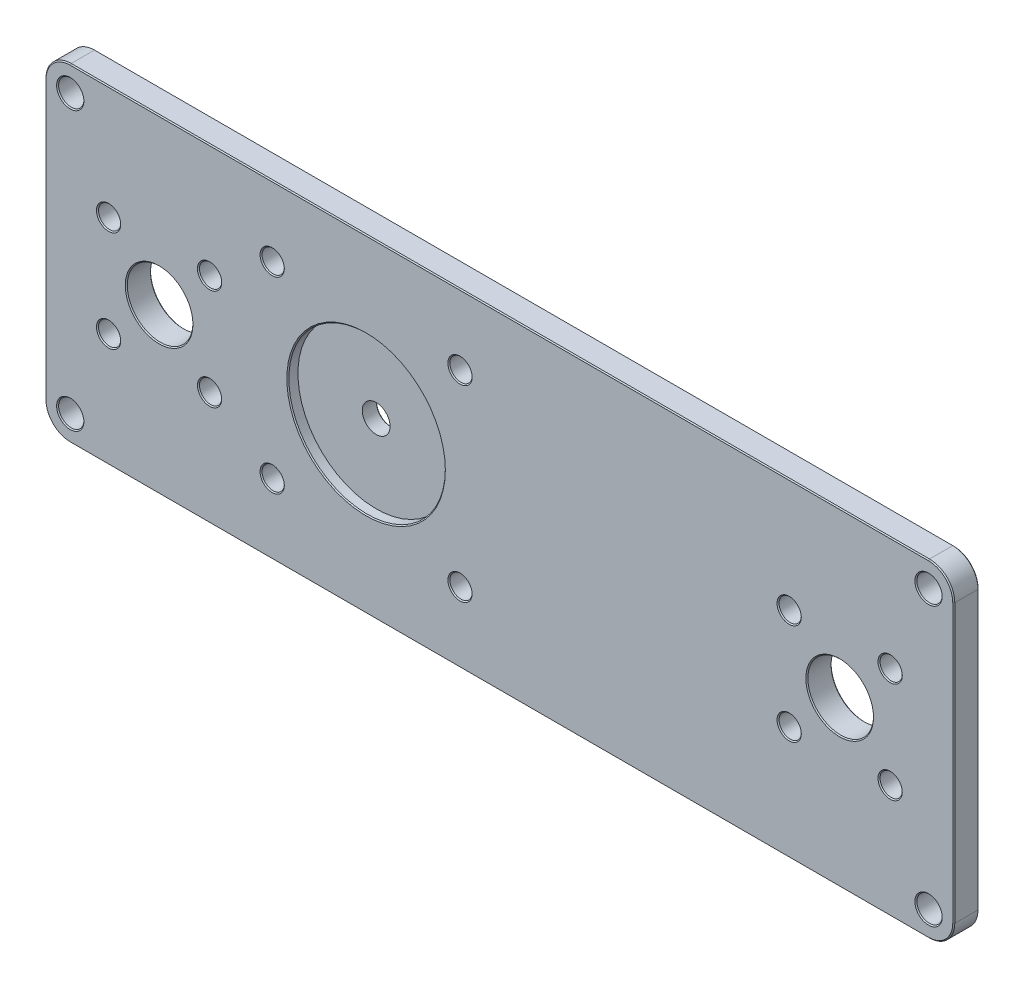
SolidWorks part; units mm, degrees
material "1060 Alloy"
ref_plane "Front Plane" through (0, 0, 0) normal (0, 0, 1) x (1, 0, 0)
ref_plane "Top Plane" through (0, 0, 0) normal (0, 1, 0) x (1, 0, 0)
ref_plane "Right Plane" through (0, 0, 0) normal (1, 0, 0) x (0, 0, -1)
sketch "Sketch3" plane through (0, 0, 0) normal (0, 0, 1) x (1, 0, 0)
  line L0 (-57.15, 23.622) -> (-57.15, -23.622) construction
  line L1 (107.95, -41.275) -> (-107.95, -41.275)
  line L2 (114.3, -34.925) -> (114.3, 34.925)
  line L3 (107.95, 41.275) -> (-107.95, 41.275)
  line L4 (-114.3, -34.925) -> (-114.3, 34.925)
  line L5 (114.3, -41.275) -> (-114.3, 41.275) construction
  line L6 (114.3, 41.275) -> (-114.3, -41.275) construction
  line L7 (-57.15, -23.622) -> (-9.906, -23.622) construction
  line L8 (-9.906, -23.622) -> (-9.906, 23.622) construction
  line L9 (-9.906, 23.622) -> (-57.15, 23.622) construction
  line L10 (-57.15, 23.622) -> (-9.906, -23.622) construction
  line L11 (-9.906, 23.622) -> (-57.15, -23.622) construction
  line L12 (72.898, 12.7) -> (72.898, -12.7) construction
  line L13 (72.898, -12.7) -> (98.298, -12.7) construction
  line L14 (98.298, -12.7) -> (98.298, 12.7) construction
  line L15 (98.298, 12.7) -> (72.898, 12.7) construction
  line L16 (72.898, 12.7) -> (98.298, -12.7) construction
  line L17 (98.298, 12.7) -> (72.898, -12.7) construction
  line L18 (-98.298, 12.7) -> (-72.898, 12.7) construction
  line L19 (-72.898, 12.7) -> (-72.898, -12.7) construction
  line L20 (-72.898, -12.7) -> (-98.298, -12.7) construction
  line L21 (-98.298, -12.7) -> (-98.298, 12.7) construction
  line L22 (-98.298, 12.7) -> (-72.898, -12.7) construction
  line L23 (-72.898, 12.7) -> (-98.298, -12.7) construction
  arc A0 (114.3, 34.925) -> (107.95, 41.275) centre (107.95, 34.925) ccw
  arc A1 (107.95, -41.275) -> (114.3, -34.925) centre (107.95, -34.925) ccw
  arc A2 (-107.95, -41.275) -> (-114.3, -34.925) centre (-107.95, -34.925) cw
  arc A3 (-107.95, 41.275) -> (-114.3, 34.925) centre (-107.95, 34.925) ccw
  circle A4 centre (-57.15, 23.622) radius 2.794
  circle A5 centre (-9.906, 23.622) radius 2.794
  circle A6 centre (-9.906, -23.622) radius 2.794
  circle A7 centre (-57.15, -23.622) radius 2.794
  circle A8 centre (-107.95, 34.925) radius 3.175
  circle A9 centre (-107.95, -34.925) radius 3.175
  circle A10 centre (107.95, -34.925) radius 3.175
  circle A11 centre (107.95, 34.925) radius 3.175
  circle A12 centre (-33.528, 0) radius 3.4925
  circle A13 centre (-33.528, 0) radius 19.685
  circle A14 centre (85.598, 0) radius 8.255
  circle A15 centre (72.898, 12.7) radius 2.794
  circle A16 centre (98.298, 12.7) radius 2.794
  circle A17 centre (98.298, -12.7) radius 2.794
  circle A18 centre (72.898, -12.7) radius 2.794
  circle A19 centre (-85.598, 0) radius 8.255
  circle A20 centre (-72.898, -12.7) radius 2.794
  circle A21 centre (-72.898, 12.7) radius 2.794
  circle A22 centre (-98.298, 12.7) radius 2.794
  circle A23 centre (-98.298, -12.7) radius 2.794
  point P0 (0, 0)
  point P22 (-114.3, 0)
  point P23 (-57.15, 0)
  point P38 (114.3, 0)
  point P43 (85.598, 0)
  point P57 (-98.298, 0)
  dimension "D3" = 6.35
  dimension "D6" = 5.588
  dimension "D7" = 6.35
  dimension "D8" = 39.37
  dimension "D9" = 6.985
  dimension "D10" = 16.51
  dimension "D11" = 28.702
  dimension "D13" = 5.588
  dimension "D14" = 25.4
  dimension "D15" = 5.588
  dimension "D16" = 16.51
  dimension "D1" = 82.55
  dimension "D2" = 228.6
  dimension "D4" = 47.244
  dimension "D5" = 57.15
  dimension "D12" = 25.4
  dimension "D17" = 28.702
extrude "Boss-Extrude1" add sketch "Sketch3" along normal blind 6.35 contours L3 A3 L4 A2 L1 A1 L2 A0 A13 A11 A10 A9 A8 A7 A6 A5 A4 region at (2.63, 0, 0)
extrude "Boss-Extrude2" add sketch "Sketch3<4>" along normal blind 3.81 contours A13 A12 region at (-52.6562, 0, 0)
sketch "Sketch3<4>" plane through (0, 0, 0) normal (0, 0, 1) x (1, 0, 0) same geometry as "Sketch3"
chamfer "Chamfer1" distance 0.254 angle 45 54 edges at (-30.0355, 0, 0) (-112.4401, 39.4151, 0) (-114.3, 0, 0) (-112.4401, -39.4151, 0) (0, -41.275, 0) (112.4401, -39.4151, 0) (114.3, 0, 0) (112.4401, 39.4151, 0) (0, 41.275, 0) (-54.356, 23.622, 0) (-7.112, 23.622, 0) (-7.112, -23.622, 0) (-54.356, -23.622, 0) (-104.775, 34.925, 0) (-104.775, -34.925, 0) (111.125, -34.925, 0) (111.125, 34.925, 0) (112.4401, 39.4151, 6.35) (114.3, 0, 6.35) (112.4401, -39.4151, 6.35) (0, -41.275, 6.35) (-112.4401, -39.4151, 6.35) (-114.3, 0, 6.35) (-112.4401, 39.4151, 6.35) (0, 41.275, 6.35) (-54.356, 23.622, 6.35) (-7.112, 23.622, 6.35) (-7.112, -23.622, 6.35) (-54.356, -23.622, 6.35) (-104.775, 34.925, 6.35) (-104.775, -34.925, 6.35) (111.125, -34.925, 6.35) (111.125, 34.925, 6.35) (-13.843, 0, 6.35) (93.853, 0, 0) (75.692, 12.7, 0) (101.092, 12.7, 0) (101.092, -12.7, 0) (75.692, -12.7, 0) (93.853, 0, 6.35) (75.692, 12.7, 6.35) (101.092, 12.7, 6.35) (101.092, -12.7, 6.35) (75.692, -12.7, 6.35) (-77.343, 0, 0) (-70.104, -12.7, 0) (-70.104, 12.7, 0) (-95.504, 12.7, 0) (-95.504, -12.7, 0) (-77.343, 0, 6.35) (-70.104, -12.7, 6.35) (-70.104, 12.7, 6.35) (-95.504, 12.7, 6.35) (-95.504, -12.7, 6.35)
